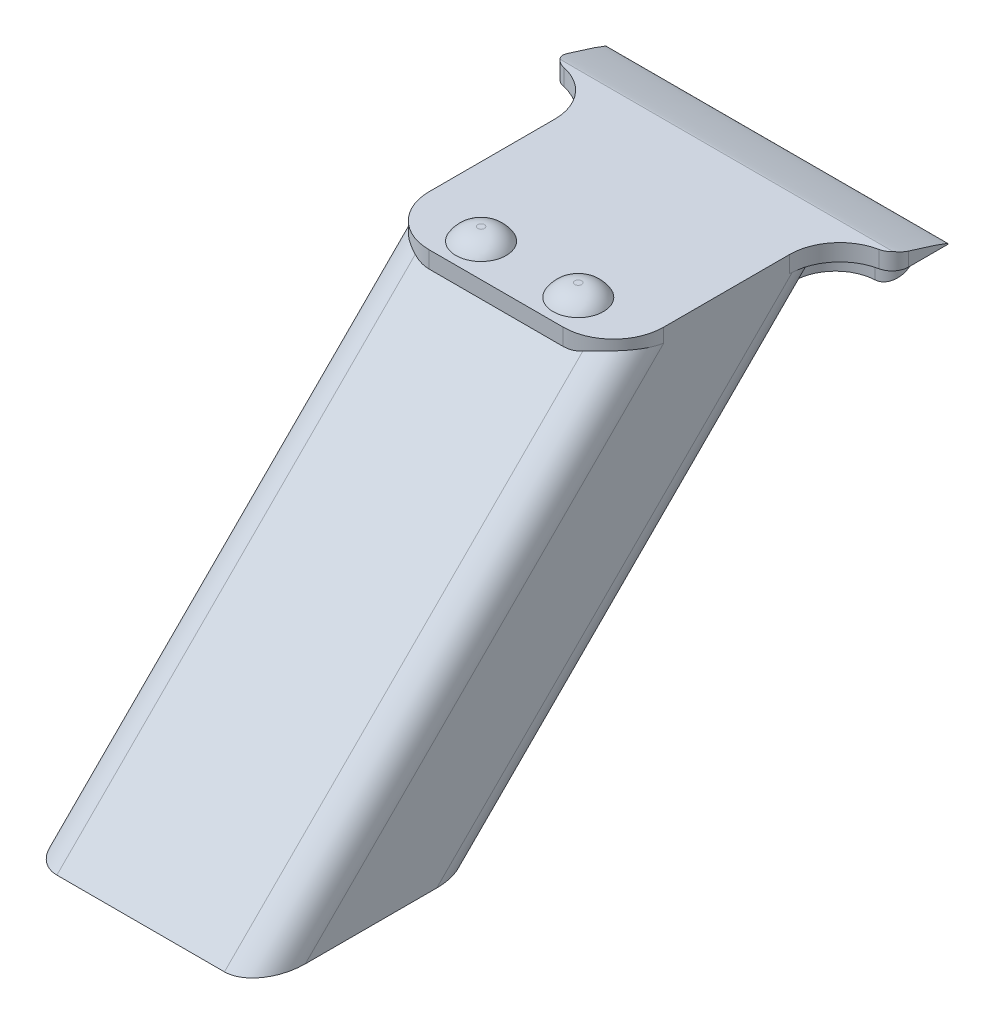
SolidWorks part; units mm, degrees
ref_plane "Front Plane" through (0, 0, 0) normal (0, 0, 1) x (1, 0, 0)
ref_plane "Top Plane" through (0, 0, 0) normal (0, 1, 0) x (1, 0, 0)
ref_plane "Right Plane" through (0, 0, 0) normal (1, 0, 0) x (0, 0, -1)
sketch "Sketch1" plane through (0, 0, 0) normal (0, 1, 0) x (1, 0, 0)
  line L1 (0, 0) -> (40.8, 0)
  line L2 (0, 0) -> (0, -6.5)
  line L3 (0, -6.5) -> (40.8, -6.5)
  line L4 (40.8, 0) -> (40.8, -6.5)
  line L5 (6.4, -6.5) -> (34.4, -6.5)
  line L6 (6.4, -6.5) -> (6.4, -33.5)
  line L7 (6.4, -33.5) -> (34.4, -33.5)
  line L8 (34.4, -6.5) -> (34.4, -33.5)
  point P11 (0, 0)
  dimension "D1" = 40.8
  dimension "D2" = 6.5
  dimension "28" = 28
  dimension "D3" = 27
  dimension "D4" = 6.4
extrude "Boss-Extrude1" add sketch "Sketch1" along normal blind 2 contours L8 L3 L6 L7 | L4 L1 L2 L3 region at (20.4, 0, 3.25) region at (20.4, 0, 20)
fillet "Fillet1" radius 6 2 edges at (34.4, 1, 6.5) (6.4, 1, 6.5)
fillet "Fillet2" radius 2 2 edges at (40.8, 1, 6.5) (0, 1, 6.5)
fillet "Fillet3" radius 6 1 edges at (20.4, 2, 0) second distance 1.9 conic rho 0.05 first distance on face at (20.4, 2, 11.3425)
sketch "Sketch2" plane through (0, 0, 0) normal (0, -1, 0) x (-1, 0, 0)
  line L0 (0, 0) -> (-40.8, 0) construction
  line L1 (-1.8, 0) -> (-39, 0)
  line L2 (-1.8, 0) -> (-1.8, -5)
  line L3 (-1.8, -5) -> (-39, -5)
  line L4 (-39, 0) -> (-39, -5)
  line L5 (-6.4, -12.5) -> (-6.4, -33.5) construction
  line L6 (-8.4, -5) -> (-32.4, -5)
  line L7 (-8.4, -5) -> (-8.4, -23)
  line L8 (-8.4, -23) -> (-32.4, -23)
  line L9 (-32.4, -5) -> (-32.4, -23)
  line L10 (-34.4, -12.5) -> (-34.4, -33.5) construction
  line M12 (0, 0) -> (-40.8, 0)
  dimension "D1" = 1.8
  dimension "D2" = 1.8
  dimension "D3" = 5
  dimension "D4" = 2
  dimension "D5" = 2
  dimension "D6" = 18
extrude "Boss-Extrude2" add sketch "Sketch2" along normal blind 3 contours L3 L9 L8 L7 | L4 L3 L2 M12 region at (20.4, 0, 2.5) region at (20.4, 0, 14)
fillet "Fillet4" radius 2.9 1 edges at (20.4, -3, 0) second distance 5 conic rho 0.05 first distance on face at (17.85, -0.7125, 0)
fillet "Fillet5" radius 5 2 edges
fillet "Fillet6" radius 2 2 edges
sketch "Sketch3" plane through (34.4, 0, 0) normal (1, 0, 0) x (0, 0, -1)
  line L0 (-33.5, 0) -> (-6.5, 0)
  line L1 (-6.5, 0) -> (-48.9264, -42.4264)
  line L2 (-33.5, 0) -> (-75.9264, -42.4264)
  line L3 (-75.9264, -42.4264) -> (-48.9264, -42.4264)
  dimension "D1" = 27
  dimension "D2" = 60
  dimension "D3" = 60
extrude "Boss-Extrude3" add sketch "Sketch3" against normal blind 28
fillet "Fillet7" radius 4 4 edges at (6.4, -21.2132, 54.7132) (34.4, -21.2132, 54.7132) (6.4, -21.2132, 27.7132) (34.4, -21.2132, 27.7132)
fillet "Fillet8" radius 6 2 edges at (6.4, -1.8284, 33.5) (34.4, -1.8284, 33.5)
sketch "Sketch4" plane through (0, 2, 0) normal (0, 1, 0) x (1, 0, 0)
  line L0 (12.4, -33.5) -> (28.4, -33.5) construction
  line L1 (34.4, -12.5) -> (34.4, -27.5) construction
  line L2 (6.4, -12.5) -> (6.4, -27.5) construction
  circle A0 centre (14.6, -29.5) radius 3
  circle A1 centre (26.2, -29.5) radius 3
  dimension "D5" = 6
  dimension "D6" = 6
  dimension "D1" = 4
  dimension "D2" = 4
  dimension "D3" = 8.2
  dimension "D4" = 8.2
extrude "Boss-Extrude4" add sketch "Sketch4" along normal blind 1.5
fillet "Fillet9" radius 3 2 edges at (26.2, 3.5, 32.5) (14.6, 3.5, 32.5)
equation "\"D4@Sketch1\"=\"D1@Sketch1\"/2-\"28@Sketch1\"/2"
